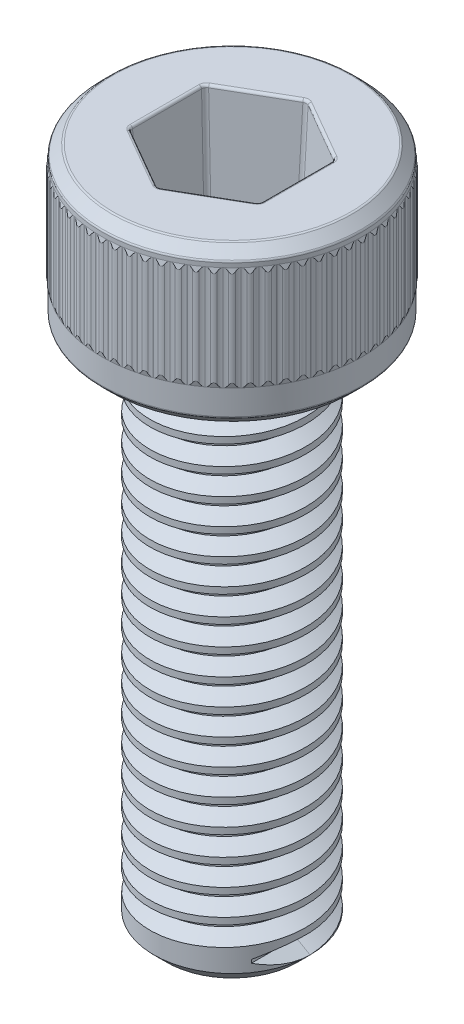
SolidWorks part; units mm, degrees
ref_plane "Спереди" through (0, 0, 0) normal (0, 0, 1) x (1, 0, 0)
ref_plane "Сверху" through (0, 0, 0) normal (0, 1, 0) x (1, 0, 0)
ref_plane "Справа" through (0, 0, 0) normal (1, 0, 0) x (0, 0, -1)
sketch "Эскиз1" plane through (0, 0, 0) normal (0, 1, 0) x (1, 0, 0)
  circle A0 centre (0, 0) radius 5
extrude "Бобышка-Вытянуть1" add sketch "Эскиз1" along normal blind 6
sketch "Эскиз2" plane through (0, 6, 0) normal (0, 1, 0) x (1, 0, 0)
  line L1 (0, 2.8868) -> (-2.5, 1.4434)
  line L2 (-2.5, 1.4434) -> (-2.5, -1.4434)
  line L3 (-2.5, -1.4434) -> (0, -2.8868)
  line L4 (0, -2.8868) -> (2.5, -1.4434)
  line L5 (2.5, -1.4434) -> (2.5, 1.4434)
  line L6 (2.5, 1.4434) -> (0, 2.8868)
  circle A0 centre (0, 0) radius 2.5 construction
extrude "Вырез-Вытянуть1" cut sketch "Эскиз2" against normal blind 4 draft 3
fillet "Скругление1" radius 0.2 6 edges at (-2.3952, 4, 1.3829) (0, 4, 2.7657) (2.3952, 4, 1.3829) (2.3952, 4, -1.3829) (0, 4, -2.7657) (-2.3952, 4, -1.3829)
fillet "Скругление2" radius 0.1 12 edges at (-2.5, 6, 0) (-2.4732, 6, 1.4279) (-1.25, 6, 2.1651) (0, 6, 2.8559) (1.25, 6, 2.1651) (2.4732, 6, 1.4279) (2.5, 6, 0) (2.4732, 6, -1.4279) (1.25, 6, -2.1651) (0, 6, -2.8559) (-1.25, 6, -2.1651) (-2.4732, 6, -1.4279)
chamfer "Фаска1" distance 0.4 angle 45 2 edges at (0, 0, 5) (0, 6, 5)
fillet "Скругление3" radius 0.1 4 edges at (0, 0, 4.6) (0, 0.4, 5) (0, 5.6, 5) (0, 6, 4.6)
sketch "Эскиз3" plane through (0, 0, 0) normal (0, -1, 0) x (1, 0, 0)
  circle A0 centre (0, 0) radius 3
extrude "Бобышка-Вытянуть2" add sketch "Эскиз3" along normal blind 20
chamfer "Фаска2" distance 0.5 angle 45 1 edges at (0, -20, -3)
thread "Резьба1" pitch 1 method cut profile "Профиль резьбы1" start angle 0, offset 0, length 0, pitch 1, diameter 6
ref_plane "Плоскость1" through (3, -19.5, 0) normal (0, 0, -1) x (-1, 0, 0)
sketch "Профиль резьбы1" plane through (3, -19.5, 0) normal (0, 0, -1) x (-1, 0, 0)
  line L0 (0, 0) -> (0, 1) construction
  line L1 (0, 0) -> (0.5413, 0.3125)
  line L2 (0.5413, 0.3125) -> (0.5413, 0.4375)
  line L3 (0.5413, 0.4375) -> (0, 0.75)
  line L4 (0.5413, 0.375) -> (0, 0.375) construction
  line L11 (0, 0) -> (0, 0.75)
  point P2 (0, 0)
  dimension "Pitch" = 1
  dimension "Profile_Angle" = 60
  dimension "Profile_Land" = 0.125
  dimension "Profile_Height" = 0.5413
sketch "Эскиз8" plane through (0, 6, 0) normal (0, 1, 0) x (1, 0, 0)
  line L0 (-0.2394, 4.9943) -> (-0.0332, 4.7532)
  line L1 (-0.0332, 4.7532) -> (0.2394, 4.9943)
  line L2 (0.2512, 4.9937) -> (0.4329, 4.7336)
  line L3 (0.4329, 4.7336) -> (0.7278, 4.9467)
  line L4 (0.7395, 4.945) -> (0.8947, 4.6684)
  line L5 (0.8947, 4.6684) -> (1.2092, 4.8516)
  line L6 (1.2206, 4.8487) -> (1.348, 4.5582)
  line L7 (1.348, 4.5582) -> (1.6789, 4.7097)
  line L8 (1.69, 4.7057) -> (1.7883, 4.4041)
  line L9 (1.7883, 4.4041) -> (2.1324, 4.5225)
  line L10 (2.1431, 4.5174) -> (2.2114, 4.2076)
  line L11 (2.2114, 4.2076) -> (2.5654, 4.2917)
  line L12 (2.5756, 4.2856) -> (2.6131, 3.9706)
  line L13 (2.6131, 3.9706) -> (2.9737, 4.0196)
  line L14 (2.9832, 4.0125) -> (2.9897, 3.6953)
  line L15 (2.9897, 3.6953) -> (3.3534, 3.7087)
  line L16 (3.3622, 3.7008) -> (3.3376, 3.3845)
  line L17 (3.3376, 3.3845) -> (3.7008, 3.3622)
  line L18 (3.7087, 3.3534) -> (3.6532, 3.0411)
  line L19 (3.6532, 3.0411) -> (4.0125, 2.9832)
  line L20 (4.0196, 2.9737) -> (3.9337, 2.6683)
  line L21 (3.9337, 2.6683) -> (4.2856, 2.5756)
  line L22 (4.2917, 2.5654) -> (4.1763, 2.2699)
  line L23 (4.1763, 2.2699) -> (4.5174, 2.1431)
  line L24 (4.5225, 2.1324) -> (4.3787, 1.8496)
  line L25 (4.3787, 1.8496) -> (4.7057, 1.69)
  line L26 (4.7097, 1.6789) -> (4.5389, 1.4116)
  line L27 (4.5389, 1.4116) -> (4.8487, 1.2206)
  line L28 (4.8516, 1.2092) -> (4.6554, 0.9599)
  line L29 (4.6554, 0.9599) -> (4.945, 0.7395)
  line L30 (4.9467, 0.7278) -> (4.7271, 0.4989)
  line L31 (4.7271, 0.4989) -> (4.9937, 0.2512)
  line L32 (4.9943, 0.2394) -> (4.7532, 0.0332)
  line L33 (4.7532, 0.0332) -> (4.9943, -0.2394)
  line L34 (4.9937, -0.2512) -> (4.7336, -0.4329)
  line L35 (4.7336, -0.4329) -> (4.9467, -0.7278)
  line L36 (4.945, -0.7395) -> (4.6684, -0.8947)
  line L37 (4.6684, -0.8947) -> (4.8516, -1.2092)
  line L38 (4.8487, -1.2206) -> (4.5582, -1.348)
  line L39 (4.5582, -1.348) -> (4.7097, -1.6789)
  line L40 (4.7057, -1.69) -> (4.4041, -1.7883)
  line L41 (4.4041, -1.7883) -> (4.5225, -2.1324)
  line L42 (4.5174, -2.1431) -> (4.2076, -2.2114)
  line L43 (4.2076, -2.2114) -> (4.2917, -2.5654)
  line L44 (4.2856, -2.5756) -> (3.9706, -2.6131)
  line L45 (3.9706, -2.6131) -> (4.0196, -2.9737)
  line L46 (4.0125, -2.9832) -> (3.6953, -2.9897)
  line L47 (3.6953, -2.9897) -> (3.7087, -3.3534)
  line L48 (3.7008, -3.3622) -> (3.3845, -3.3376)
  line L49 (3.3845, -3.3376) -> (3.3622, -3.7008)
  line L50 (3.3534, -3.7087) -> (3.0411, -3.6532)
  line L51 (3.0411, -3.6532) -> (2.9832, -4.0125)
  line L52 (2.9737, -4.0196) -> (2.6683, -3.9337)
  line L53 (2.6683, -3.9337) -> (2.5756, -4.2856)
  line L54 (2.5654, -4.2917) -> (2.2699, -4.1763)
  line L55 (2.2699, -4.1763) -> (2.1431, -4.5174)
  line L56 (2.1324, -4.5225) -> (1.8496, -4.3787)
  line L57 (1.8496, -4.3787) -> (1.69, -4.7057)
  line L58 (1.6789, -4.7097) -> (1.4116, -4.5389)
  line L59 (1.4116, -4.5389) -> (1.2206, -4.8487)
  line L60 (1.2092, -4.8516) -> (0.9599, -4.6554)
  line L61 (0.9599, -4.6554) -> (0.7395, -4.945)
  line L62 (0.7278, -4.9467) -> (0.4989, -4.7271)
  line L63 (0.4989, -4.7271) -> (0.2512, -4.9937)
  line L64 (0.2394, -4.9943) -> (0.0332, -4.7532)
  line L65 (0.0332, -4.7532) -> (-0.2394, -4.9943)
  line L66 (-0.2512, -4.9937) -> (-0.4329, -4.7336)
  line L67 (-0.4329, -4.7336) -> (-0.7278, -4.9467)
  line L68 (-0.7395, -4.945) -> (-0.8947, -4.6684)
  line L69 (-0.8947, -4.6684) -> (-1.2092, -4.8516)
  line L70 (-1.2206, -4.8487) -> (-1.348, -4.5582)
  line L71 (-1.348, -4.5582) -> (-1.6789, -4.7097)
  line L72 (-1.69, -4.7057) -> (-1.7883, -4.4041)
  line L73 (-1.7883, -4.4041) -> (-2.1324, -4.5225)
  line L74 (-2.1431, -4.5174) -> (-2.2114, -4.2076)
  line L75 (-2.2114, -4.2076) -> (-2.5654, -4.2917)
  line L76 (-2.5756, -4.2856) -> (-2.6131, -3.9706)
  line L77 (-2.6131, -3.9706) -> (-2.9737, -4.0196)
  line L78 (-2.9832, -4.0125) -> (-2.9897, -3.6953)
  line L79 (-2.9897, -3.6953) -> (-3.3534, -3.7087)
  line L80 (-3.3622, -3.7008) -> (-3.3376, -3.3845)
  line L81 (-3.3376, -3.3845) -> (-3.7008, -3.3622)
  line L82 (-3.7087, -3.3534) -> (-3.6532, -3.0411)
  line L83 (-3.6532, -3.0411) -> (-4.0125, -2.9832)
  line L84 (-4.0196, -2.9737) -> (-3.9337, -2.6683)
  line L85 (-3.9337, -2.6683) -> (-4.2856, -2.5756)
  line L86 (-4.2917, -2.5654) -> (-4.1763, -2.2699)
  line L87 (-4.1763, -2.2699) -> (-4.5174, -2.1431)
  line L88 (-4.5225, -2.1324) -> (-4.3787, -1.8496)
  line L89 (-4.3787, -1.8496) -> (-4.7057, -1.69)
  line L90 (-4.7097, -1.6789) -> (-4.5389, -1.4116)
  line L91 (-4.5389, -1.4116) -> (-4.8487, -1.2206)
  line L92 (-4.8516, -1.2092) -> (-4.6554, -0.9599)
  line L93 (-4.6554, -0.9599) -> (-4.945, -0.7395)
  line L94 (-4.9467, -0.7278) -> (-4.7271, -0.4989)
  line L95 (-4.7271, -0.4989) -> (-4.9937, -0.2512)
  line L96 (-4.9943, -0.2394) -> (-4.7532, -0.0332)
  line L97 (-4.7532, -0.0332) -> (-4.9943, 0.2394)
  line L98 (-4.9937, 0.2512) -> (-4.7336, 0.4329)
  line L99 (-4.7336, 0.4329) -> (-4.9467, 0.7278)
  line L100 (-4.945, 0.7395) -> (-4.6684, 0.8947)
  line L101 (-4.6684, 0.8947) -> (-4.8516, 1.2092)
  line L102 (-4.8487, 1.2206) -> (-4.5582, 1.348)
  line L103 (-4.5582, 1.348) -> (-4.7097, 1.6789)
  line L104 (-4.7057, 1.69) -> (-4.4041, 1.7883)
  line L105 (-4.4041, 1.7883) -> (-4.5225, 2.1324)
  line L106 (-4.5174, 2.1431) -> (-4.2076, 2.2114)
  line L107 (-4.2076, 2.2114) -> (-4.2917, 2.5654)
  line L108 (-4.2856, 2.5756) -> (-3.9706, 2.6131)
  line L109 (-3.9706, 2.6131) -> (-4.0196, 2.9737)
  line L110 (-4.0125, 2.9832) -> (-3.6953, 2.9897)
  line L111 (-3.6953, 2.9897) -> (-3.7087, 3.3534)
  line L112 (-3.7008, 3.3622) -> (-3.3845, 3.3376)
  line L113 (-3.3845, 3.3376) -> (-3.3622, 3.7008)
  line L114 (-3.3534, 3.7087) -> (-3.0411, 3.6532)
  line L115 (-3.0411, 3.6532) -> (-2.9832, 4.0125)
  line L116 (-2.9737, 4.0196) -> (-2.6683, 3.9337)
  line L117 (-2.6683, 3.9337) -> (-2.5756, 4.2856)
  line L118 (-2.5654, 4.2917) -> (-2.2699, 4.1763)
  line L119 (-2.2699, 4.1763) -> (-2.1431, 4.5174)
  line L120 (-2.1324, 4.5225) -> (-1.8496, 4.3787)
  line L121 (-1.8496, 4.3787) -> (-1.69, 4.7057)
  line L122 (-1.6789, 4.7097) -> (-1.4116, 4.5389)
  line L123 (-1.4116, 4.5389) -> (-1.2206, 4.8487)
  line L124 (-1.2092, 4.8516) -> (-0.9599, 4.6554)
  line L125 (-0.9599, 4.6554) -> (-0.7395, 4.945)
  line L126 (-0.7278, 4.9467) -> (-0.4989, 4.7271)
  line L127 (-0.4989, 4.7271) -> (-0.2512, 4.9937)
  arc A1 (0.0913, 5.0242) -> (-0.0913, 5.0242) centre (0, 4.7752) ccw
  arc A2 (0.5833, 4.9911) -> (0.4016, 5.009) centre (0.468, 4.7522) ccw
  arc A3 (0.2394, 4.9943) -> (0.0913, 5.0242) centre (0.2634, 5.4937) cw
  arc A4 (-0.2394, 4.9943) -> (-0.0913, 5.0242) centre (-0.2634, 5.4937) ccw
  arc A5 (0.7278, 4.9467) -> (0.5833, 4.9911) centre (0.8006, 5.4414) cw
  arc A6 (0.2512, 4.9937) -> (0.4016, 5.009) centre (0.2764, 5.4931) ccw
  arc A7 (1.0697, 4.9099) -> (0.8906, 4.9455) centre (0.9316, 4.6834) ccw
  arc A8 (1.2092, 4.8516) -> (1.0697, 4.9099) centre (1.3301, 5.3367) cw
  arc A9 (0.7395, 4.945) -> (0.8906, 4.9455) centre (0.8135, 5.4395) ccw
  arc A10 (1.5458, 4.7814) -> (1.3711, 4.8344) centre (1.3862, 4.5696) ccw
  arc A11 (1.6789, 4.7097) -> (1.5458, 4.7814) centre (1.8468, 5.1807) cw
  arc A12 (1.2206, 4.8487) -> (1.3711, 4.8344) centre (1.3427, 5.3336) ccw
  arc A13 (2.007, 4.6069) -> (1.8383, 4.6767) centre (1.8274, 4.4117) ccw
  arc A14 (2.1324, 4.5225) -> (2.007, 4.6069) centre (2.3457, 4.9747) cw
  arc A15 (1.69, 4.7057) -> (1.8383, 4.6767) centre (1.859, 5.1763) ccw
  arc A16 (2.4489, 4.3879) -> (2.2879, 4.474) centre (2.251, 4.2113) ccw
  arc A17 (2.5654, 4.2917) -> (2.4489, 4.3879) centre (2.822, 4.7208) cw
  arc A18 (2.1431, 4.5174) -> (2.2879, 4.474) centre (2.3574, 4.9692) ccw
  arc A19 (2.8672, 4.1268) -> (2.7154, 4.2282) centre (2.6529, 3.9704) ccw
  arc A20 (2.9737, 4.0196) -> (2.8672, 4.1268) centre (3.2711, 4.4215) cw
  arc A21 (2.5756, 4.2856) -> (2.7154, 4.2282) centre (2.8331, 4.7142) ccw
  arc A22 (3.2579, 3.8259) -> (3.1168, 3.9417) centre (3.0293, 3.6913) ccw
  arc A23 (3.3534, 3.7087) -> (3.2579, 3.8259) centre (3.6887, 4.0796) cw
  arc A24 (2.9832, 4.0125) -> (3.1168, 3.9417) centre (3.2816, 4.4138) ccw
  arc A25 (3.6172, 3.4881) -> (3.4881, 3.6172) centre (3.3766, 3.3766) ccw
  arc A26 (3.7008, 3.3622) -> (3.6172, 3.4881) centre (4.0709, 3.6984) cw
  arc A27 (3.3622, 3.7008) -> (3.4881, 3.6172) centre (3.6984, 4.0709) ccw
  arc A28 (3.9417, 3.1168) -> (3.8259, 3.2579) centre (3.6913, 3.0293) ccw
  arc A29 (4.0125, 2.9832) -> (3.9417, 3.1168) centre (4.4138, 3.2816) cw
  arc A30 (3.7087, 3.3534) -> (3.8259, 3.2579) centre (4.0796, 3.6887) ccw
  arc A31 (4.2282, 2.7154) -> (4.1268, 2.8672) centre (3.9704, 2.6529) ccw
  arc A32 (4.2856, 2.5756) -> (4.2282, 2.7154) centre (4.7142, 2.8331) cw
  arc A33 (4.0196, 2.9737) -> (4.1268, 2.8672) centre (4.4215, 3.2711) ccw
  arc A34 (4.474, 2.2879) -> (4.3879, 2.4489) centre (4.2113, 2.251) ccw
  arc A35 (4.5174, 2.1431) -> (4.474, 2.2879) centre (4.9692, 2.3574) cw
  arc A36 (4.2917, 2.5654) -> (4.3879, 2.4489) centre (4.7208, 2.822) ccw
  arc A37 (4.6767, 1.8383) -> (4.6069, 2.007) centre (4.4117, 1.8274) ccw
  arc A38 (4.7057, 1.69) -> (4.6767, 1.8383) centre (5.1763, 1.859) cw
  arc A39 (4.5225, 2.1324) -> (4.6069, 2.007) centre (4.9747, 2.3457) ccw
  arc A40 (4.8344, 1.3711) -> (4.7814, 1.5458) centre (4.5696, 1.3862) ccw
  arc A41 (4.8487, 1.2206) -> (4.8344, 1.3711) centre (5.3336, 1.3427) cw
  arc A42 (4.7097, 1.6789) -> (4.7814, 1.5458) centre (5.1807, 1.8468) ccw
  arc A43 (4.9455, 0.8906) -> (4.9099, 1.0697) centre (4.6834, 0.9316) ccw
  arc A44 (4.945, 0.7395) -> (4.9455, 0.8906) centre (5.4395, 0.8135) cw
  arc A45 (4.8516, 1.2092) -> (4.9099, 1.0697) centre (5.3367, 1.3301) ccw
  arc A46 (5.009, 0.4016) -> (4.9911, 0.5833) centre (4.7522, 0.468) ccw
  arc A47 (4.9937, 0.2512) -> (5.009, 0.4016) centre (5.4931, 0.2764) cw
  arc A48 (4.9467, 0.7278) -> (4.9911, 0.5833) centre (5.4414, 0.8006) ccw
  arc A49 (5.0242, -0.0913) -> (5.0242, 0.0913) centre (4.7752, 0) ccw
  arc A50 (4.9943, -0.2394) -> (5.0242, -0.0913) centre (5.4937, -0.2634) cw
  arc A51 (4.9943, 0.2394) -> (5.0242, 0.0913) centre (5.4937, 0.2634) ccw
  arc A52 (4.9911, -0.5833) -> (5.009, -0.4016) centre (4.7522, -0.468) ccw
  arc A53 (4.9467, -0.7278) -> (4.9911, -0.5833) centre (5.4414, -0.8006) cw
  arc A54 (4.9937, -0.2512) -> (5.009, -0.4016) centre (5.4931, -0.2764) ccw
  arc A55 (4.9099, -1.0697) -> (4.9455, -0.8906) centre (4.6834, -0.9316) ccw
  arc A56 (4.8516, -1.2092) -> (4.9099, -1.0697) centre (5.3367, -1.3301) cw
  arc A57 (4.945, -0.7395) -> (4.9455, -0.8906) centre (5.4395, -0.8135) ccw
  arc A58 (4.7814, -1.5458) -> (4.8344, -1.3711) centre (4.5696, -1.3862) ccw
  arc A59 (4.7097, -1.6789) -> (4.7814, -1.5458) centre (5.1807, -1.8468) cw
  arc A60 (4.8487, -1.2206) -> (4.8344, -1.3711) centre (5.3336, -1.3427) ccw
  arc A61 (4.6069, -2.007) -> (4.6767, -1.8383) centre (4.4117, -1.8274) ccw
  arc A62 (4.5225, -2.1324) -> (4.6069, -2.007) centre (4.9747, -2.3457) cw
  arc A63 (4.7057, -1.69) -> (4.6767, -1.8383) centre (5.1763, -1.859) ccw
  arc A64 (4.3879, -2.4489) -> (4.474, -2.2879) centre (4.2113, -2.251) ccw
  arc A65 (4.2917, -2.5654) -> (4.3879, -2.4489) centre (4.7208, -2.822) cw
  arc A66 (4.5174, -2.1431) -> (4.474, -2.2879) centre (4.9692, -2.3574) ccw
  arc A67 (4.1268, -2.8672) -> (4.2282, -2.7154) centre (3.9704, -2.6529) ccw
  arc A68 (4.0196, -2.9737) -> (4.1268, -2.8672) centre (4.4215, -3.2711) cw
  arc A69 (4.2856, -2.5756) -> (4.2282, -2.7154) centre (4.7142, -2.8331) ccw
  arc A70 (3.8259, -3.2579) -> (3.9417, -3.1168) centre (3.6913, -3.0293) ccw
  arc A71 (3.7087, -3.3534) -> (3.8259, -3.2579) centre (4.0796, -3.6887) cw
  arc A72 (4.0125, -2.9832) -> (3.9417, -3.1168) centre (4.4138, -3.2816) ccw
  arc A73 (3.4881, -3.6172) -> (3.6172, -3.4881) centre (3.3766, -3.3766) ccw
  arc A74 (3.3622, -3.7008) -> (3.4881, -3.6172) centre (3.6984, -4.0709) cw
  arc A75 (3.7008, -3.3622) -> (3.6172, -3.4881) centre (4.0709, -3.6984) ccw
  arc A76 (3.1168, -3.9417) -> (3.2579, -3.8259) centre (3.0293, -3.6913) ccw
  arc A77 (2.9832, -4.0125) -> (3.1168, -3.9417) centre (3.2816, -4.4138) cw
  arc A78 (3.3534, -3.7087) -> (3.2579, -3.8259) centre (3.6887, -4.0796) ccw
  arc A79 (2.7154, -4.2282) -> (2.8672, -4.1268) centre (2.6529, -3.9704) ccw
  arc A80 (2.5756, -4.2856) -> (2.7154, -4.2282) centre (2.8331, -4.7142) cw
  arc A81 (2.9737, -4.0196) -> (2.8672, -4.1268) centre (3.2711, -4.4215) ccw
  arc A82 (2.2879, -4.474) -> (2.4489, -4.3879) centre (2.251, -4.2113) ccw
  arc A83 (2.1431, -4.5174) -> (2.2879, -4.474) centre (2.3574, -4.9692) cw
  arc A84 (2.5654, -4.2917) -> (2.4489, -4.3879) centre (2.822, -4.7208) ccw
  arc A85 (1.8383, -4.6767) -> (2.007, -4.6069) centre (1.8274, -4.4117) ccw
  arc A86 (1.69, -4.7057) -> (1.8383, -4.6767) centre (1.859, -5.1763) cw
  arc A87 (2.1324, -4.5225) -> (2.007, -4.6069) centre (2.3457, -4.9747) ccw
  arc A88 (1.3711, -4.8344) -> (1.5458, -4.7814) centre (1.3862, -4.5696) ccw
  arc A89 (1.2206, -4.8487) -> (1.3711, -4.8344) centre (1.3427, -5.3336) cw
  arc A90 (1.6789, -4.7097) -> (1.5458, -4.7814) centre (1.8468, -5.1807) ccw
  arc A91 (0.8906, -4.9455) -> (1.0697, -4.9099) centre (0.9316, -4.6834) ccw
  arc A92 (0.7395, -4.945) -> (0.8906, -4.9455) centre (0.8135, -5.4395) cw
  arc A93 (1.2092, -4.8516) -> (1.0697, -4.9099) centre (1.3301, -5.3367) ccw
  arc A94 (0.4016, -5.009) -> (0.5833, -4.9911) centre (0.468, -4.7522) ccw
  arc A95 (0.2512, -4.9937) -> (0.4016, -5.009) centre (0.2764, -5.4931) cw
  arc A96 (0.7278, -4.9467) -> (0.5833, -4.9911) centre (0.8006, -5.4414) ccw
  arc A97 (-0.0913, -5.0242) -> (0.0913, -5.0242) centre (0, -4.7752) ccw
  arc A98 (-0.2394, -4.9943) -> (-0.0913, -5.0242) centre (-0.2634, -5.4937) cw
  arc A99 (0.2394, -4.9943) -> (0.0913, -5.0242) centre (0.2634, -5.4937) ccw
  arc A100 (-0.5833, -4.9911) -> (-0.4016, -5.009) centre (-0.468, -4.7522) ccw
  arc A101 (-0.7278, -4.9467) -> (-0.5833, -4.9911) centre (-0.8006, -5.4414) cw
  arc A102 (-0.2512, -4.9937) -> (-0.4016, -5.009) centre (-0.2764, -5.4931) ccw
  arc A103 (-1.0697, -4.9099) -> (-0.8906, -4.9455) centre (-0.9316, -4.6834) ccw
  arc A104 (-1.2092, -4.8516) -> (-1.0697, -4.9099) centre (-1.3301, -5.3367) cw
  arc A105 (-0.7395, -4.945) -> (-0.8906, -4.9455) centre (-0.8135, -5.4395) ccw
  arc A106 (-1.5458, -4.7814) -> (-1.3711, -4.8344) centre (-1.3862, -4.5696) ccw
  arc A107 (-1.6789, -4.7097) -> (-1.5458, -4.7814) centre (-1.8468, -5.1807) cw
  arc A108 (-1.2206, -4.8487) -> (-1.3711, -4.8344) centre (-1.3427, -5.3336) ccw
  arc A109 (-2.007, -4.6069) -> (-1.8383, -4.6767) centre (-1.8274, -4.4117) ccw
  arc A110 (-2.1324, -4.5225) -> (-2.007, -4.6069) centre (-2.3457, -4.9747) cw
  arc A111 (-1.69, -4.7057) -> (-1.8383, -4.6767) centre (-1.859, -5.1763) ccw
  arc A112 (-2.4489, -4.3879) -> (-2.2879, -4.474) centre (-2.251, -4.2113) ccw
  arc A113 (-2.5654, -4.2917) -> (-2.4489, -4.3879) centre (-2.822, -4.7208) cw
  arc A114 (-2.1431, -4.5174) -> (-2.2879, -4.474) centre (-2.3574, -4.9692) ccw
  arc A115 (-2.8672, -4.1268) -> (-2.7154, -4.2282) centre (-2.6529, -3.9704) ccw
  arc A116 (-2.9737, -4.0196) -> (-2.8672, -4.1268) centre (-3.2711, -4.4215) cw
  arc A117 (-2.5756, -4.2856) -> (-2.7154, -4.2282) centre (-2.8331, -4.7142) ccw
  arc A118 (-3.2579, -3.8259) -> (-3.1168, -3.9417) centre (-3.0293, -3.6913) ccw
  arc A119 (-3.3534, -3.7087) -> (-3.2579, -3.8259) centre (-3.6887, -4.0796) cw
  arc A120 (-2.9832, -4.0125) -> (-3.1168, -3.9417) centre (-3.2816, -4.4138) ccw
  arc A121 (-3.6172, -3.4881) -> (-3.4881, -3.6172) centre (-3.3766, -3.3766) ccw
  arc A122 (-3.7008, -3.3622) -> (-3.6172, -3.4881) centre (-4.0709, -3.6984) cw
  arc A123 (-3.3622, -3.7008) -> (-3.4881, -3.6172) centre (-3.6984, -4.0709) ccw
  arc A124 (-3.9417, -3.1168) -> (-3.8259, -3.2579) centre (-3.6913, -3.0293) ccw
  arc A125 (-4.0125, -2.9832) -> (-3.9417, -3.1168) centre (-4.4138, -3.2816) cw
  arc A126 (-3.7087, -3.3534) -> (-3.8259, -3.2579) centre (-4.0796, -3.6887) ccw
  arc A127 (-4.2282, -2.7154) -> (-4.1268, -2.8672) centre (-3.9704, -2.6529) ccw
  arc A128 (-4.2856, -2.5756) -> (-4.2282, -2.7154) centre (-4.7142, -2.8331) cw
  arc A129 (-4.0196, -2.9737) -> (-4.1268, -2.8672) centre (-4.4215, -3.2711) ccw
  arc A130 (-4.474, -2.2879) -> (-4.3879, -2.4489) centre (-4.2113, -2.251) ccw
  arc A131 (-4.5174, -2.1431) -> (-4.474, -2.2879) centre (-4.9692, -2.3574) cw
  arc A132 (-4.2917, -2.5654) -> (-4.3879, -2.4489) centre (-4.7208, -2.822) ccw
  arc A133 (-4.6767, -1.8383) -> (-4.6069, -2.007) centre (-4.4117, -1.8274) ccw
  arc A134 (-4.7057, -1.69) -> (-4.6767, -1.8383) centre (-5.1763, -1.859) cw
  arc A135 (-4.5225, -2.1324) -> (-4.6069, -2.007) centre (-4.9747, -2.3457) ccw
  arc A136 (-4.8344, -1.3711) -> (-4.7814, -1.5458) centre (-4.5696, -1.3862) ccw
  arc A137 (-4.8487, -1.2206) -> (-4.8344, -1.3711) centre (-5.3336, -1.3427) cw
  arc A138 (-4.7097, -1.6789) -> (-4.7814, -1.5458) centre (-5.1807, -1.8468) ccw
  arc A139 (-4.9455, -0.8906) -> (-4.9099, -1.0697) centre (-4.6834, -0.9316) ccw
  arc A140 (-4.945, -0.7395) -> (-4.9455, -0.8906) centre (-5.4395, -0.8135) cw
  arc A141 (-4.8516, -1.2092) -> (-4.9099, -1.0697) centre (-5.3367, -1.3301) ccw
  arc A142 (-5.009, -0.4016) -> (-4.9911, -0.5833) centre (-4.7522, -0.468) ccw
  arc A143 (-4.9937, -0.2512) -> (-5.009, -0.4016) centre (-5.4931, -0.2764) cw
  arc A144 (-4.9467, -0.7278) -> (-4.9911, -0.5833) centre (-5.4414, -0.8006) ccw
  arc A145 (-5.0242, 0.0913) -> (-5.0242, -0.0913) centre (-4.7752, 0) ccw
  arc A146 (-4.9943, 0.2394) -> (-5.0242, 0.0913) centre (-5.4937, 0.2634) cw
  arc A147 (-4.9943, -0.2394) -> (-5.0242, -0.0913) centre (-5.4937, -0.2634) ccw
  arc A148 (-4.9911, 0.5833) -> (-5.009, 0.4016) centre (-4.7522, 0.468) ccw
  arc A149 (-4.9467, 0.7278) -> (-4.9911, 0.5833) centre (-5.4414, 0.8006) cw
  arc A150 (-4.9937, 0.2512) -> (-5.009, 0.4016) centre (-5.4931, 0.2764) ccw
  arc A151 (-4.9099, 1.0697) -> (-4.9455, 0.8906) centre (-4.6834, 0.9316) ccw
  arc A152 (-4.8516, 1.2092) -> (-4.9099, 1.0697) centre (-5.3367, 1.3301) cw
  arc A153 (-4.945, 0.7395) -> (-4.9455, 0.8906) centre (-5.4395, 0.8135) ccw
  arc A154 (-4.7814, 1.5458) -> (-4.8344, 1.3711) centre (-4.5696, 1.3862) ccw
  arc A155 (-4.7097, 1.6789) -> (-4.7814, 1.5458) centre (-5.1807, 1.8468) cw
  arc A156 (-4.8487, 1.2206) -> (-4.8344, 1.3711) centre (-5.3336, 1.3427) ccw
  arc A157 (-4.6069, 2.007) -> (-4.6767, 1.8383) centre (-4.4117, 1.8274) ccw
  arc A158 (-4.5225, 2.1324) -> (-4.6069, 2.007) centre (-4.9747, 2.3457) cw
  arc A159 (-4.7057, 1.69) -> (-4.6767, 1.8383) centre (-5.1763, 1.859) ccw
  arc A160 (-4.3879, 2.4489) -> (-4.474, 2.2879) centre (-4.2113, 2.251) ccw
  arc A161 (-4.2917, 2.5654) -> (-4.3879, 2.4489) centre (-4.7208, 2.822) cw
  arc A162 (-4.5174, 2.1431) -> (-4.474, 2.2879) centre (-4.9692, 2.3574) ccw
  arc A163 (-4.1268, 2.8672) -> (-4.2282, 2.7154) centre (-3.9704, 2.6529) ccw
  arc A164 (-4.0196, 2.9737) -> (-4.1268, 2.8672) centre (-4.4215, 3.2711) cw
  arc A165 (-4.2856, 2.5756) -> (-4.2282, 2.7154) centre (-4.7142, 2.8331) ccw
  arc A166 (-3.8259, 3.2579) -> (-3.9417, 3.1168) centre (-3.6913, 3.0293) ccw
  arc A167 (-3.7087, 3.3534) -> (-3.8259, 3.2579) centre (-4.0796, 3.6887) cw
  arc A168 (-4.0125, 2.9832) -> (-3.9417, 3.1168) centre (-4.4138, 3.2816) ccw
  arc A169 (-3.4881, 3.6172) -> (-3.6172, 3.4881) centre (-3.3766, 3.3766) ccw
  arc A170 (-3.3622, 3.7008) -> (-3.4881, 3.6172) centre (-3.6984, 4.0709) cw
  arc A171 (-3.7008, 3.3622) -> (-3.6172, 3.4881) centre (-4.0709, 3.6984) ccw
  arc A172 (-3.1168, 3.9417) -> (-3.2579, 3.8259) centre (-3.0293, 3.6913) ccw
  arc A173 (-2.9832, 4.0125) -> (-3.1168, 3.9417) centre (-3.2816, 4.4138) cw
  arc A174 (-3.3534, 3.7087) -> (-3.2579, 3.8259) centre (-3.6887, 4.0796) ccw
  arc A175 (-2.7154, 4.2282) -> (-2.8672, 4.1268) centre (-2.6529, 3.9704) ccw
  arc A176 (-2.5756, 4.2856) -> (-2.7154, 4.2282) centre (-2.8331, 4.7142) cw
  arc A177 (-2.9737, 4.0196) -> (-2.8672, 4.1268) centre (-3.2711, 4.4215) ccw
  arc A178 (-2.2879, 4.474) -> (-2.4489, 4.3879) centre (-2.251, 4.2113) ccw
  arc A179 (-2.1431, 4.5174) -> (-2.2879, 4.474) centre (-2.3574, 4.9692) cw
  arc A180 (-2.5654, 4.2917) -> (-2.4489, 4.3879) centre (-2.822, 4.7208) ccw
  arc A181 (-1.8383, 4.6767) -> (-2.007, 4.6069) centre (-1.8274, 4.4117) ccw
  arc A182 (-1.69, 4.7057) -> (-1.8383, 4.6767) centre (-1.859, 5.1763) cw
  arc A183 (-2.1324, 4.5225) -> (-2.007, 4.6069) centre (-2.3457, 4.9747) ccw
  arc A184 (-1.3711, 4.8344) -> (-1.5458, 4.7814) centre (-1.3862, 4.5696) ccw
  arc A185 (-1.2206, 4.8487) -> (-1.3711, 4.8344) centre (-1.3427, 5.3336) cw
  arc A186 (-1.6789, 4.7097) -> (-1.5458, 4.7814) centre (-1.8468, 5.1807) ccw
  arc A187 (-0.8906, 4.9455) -> (-1.0697, 4.9099) centre (-0.9316, 4.6834) ccw
  arc A188 (-0.7395, 4.945) -> (-0.8906, 4.9455) centre (-0.8135, 5.4395) cw
  arc A189 (-1.2092, 4.8516) -> (-1.0697, 4.9099) centre (-1.3301, 5.3367) ccw
  arc A190 (-0.4016, 5.009) -> (-0.5833, 4.9911) centre (-0.468, 4.7522) ccw
  arc A191 (-0.2512, 4.9937) -> (-0.4016, 5.009) centre (-0.2764, 5.4931) cw
  arc A192 (-0.7278, 4.9467) -> (-0.5833, 4.9911) centre (-0.8006, 5.4414) ccw
  point P516 (0, 0)
extrude "Бобышка-Вытянуть3" add sketch "Эскиз8" against normal blind 4 from offset 0.6 offset against normal yes
sketch "Эскиз9" plane through (0, 0, 0) normal (1, 0, 0) x (0, 0, -1)
  line L0 (5, 5.4) -> (5.0404, 5.2114)
  line L3 (5.0404, 5.2114) -> (5.0404, 5.4)
  line L5 (5.0404, 5.4) -> (5, 5.4)
  line L6 (-4.5641, 3.4) -> (49995.4359, 3.4) construction
  line L8 (5.0404, 1.4) -> (5, 1.4)
  line L9 (5.0404, 1.5886) -> (5.0404, 1.4)
  line L10 (5, 1.4) -> (5.0404, 1.5886)
  line L11 (0, 0) -> (0, 50000) construction
revolve "Вырез-Повернуть1" cut sketch "Эскиз9" angle 360 about L11
sketch "Эскиз10" plane through (0, 0, 0) normal (0, 0, -1) x (-1, 0, 0)
  line L4 (-2.4587, -19.1875) -> (-2.4587, -19.0625)
  line L5 (-2.4587, -19.0625) -> (-3, -18.75)
  line L6 (-3, -18.75) -> (-3, -19.5)
  line L7 (-3, -19.5) -> (-2.4587, -19.1875)
  line L8 (-2.4587, -19.1875) -> (-2.4587, -19.0625)
  line L9 (-2.4587, -19.0625) -> (-3, -18.75)
  line L10 (-3, -18.75) -> (-3, -19.5)
  line L11 (-3, -19.5) -> (-2.4587, -19.1875)
  dimension "D1" = 0
extrude "Вырез-Вытянуть2" cut sketch "Эскиз10" against normal through all
